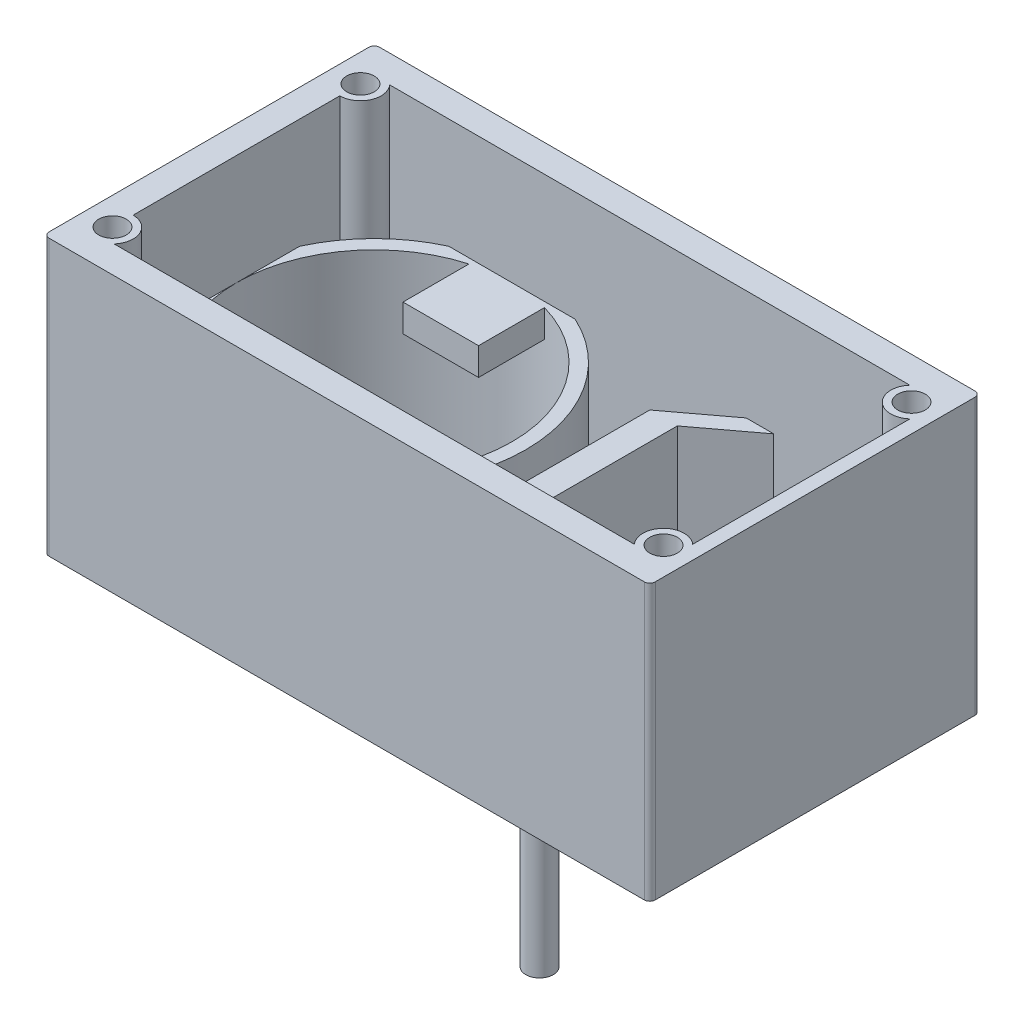
SolidWorks part; units mm, degrees
ref_plane "Front Plane" through (0, 0, 0) normal (0, 0, 1) x (1, 0, 0)
ref_plane "Top Plane" through (0, 0, 0) normal (0, 1, 0) x (1, 0, 0)
ref_plane "Right Plane" through (0, 0, 0) normal (1, 0, 0) x (0, 0, -1)
sketch "Sketch1" plane through (0, 0, 0) normal (0, 1, 0) x (1, 0, 0)
  line L1 (-11, -6) -> (11, -6)
  line L2 (-11, -6) -> (-11, 6)
  line L3 (-11, 6) -> (11, 6)
  line L4 (11, -6) -> (11, 6)
  line L5 (-11, -6) -> (11, 6) construction
  line L6 (-11, 6) -> (11, -6) construction
  point P0 (0, 0)
  dimension "D1" = 12
  dimension "D2" = 22
extrude "Boss-Extrude1" add sketch "Sketch1" along normal blind 10
sketch "Sketch2" plane through (0, 10, 0) normal (0, 1, 0) x (1, 0, 0)
  line L0 (11, 6) -> (-11, 6) construction
  line L1 (10.5, -5) -> (-10, -5)
  line L2 (10.5, -5) -> (10.5, 5)
  line L3 (10.5, 5) -> (-10, 5)
  line L4 (-10, -5) -> (-10, 5)
  line L5 (10.5, -5) -> (-10, 5) construction
  line L6 (10.5, 5) -> (-10, -5) construction
  line L7 (11, -6) -> (11, 6) construction
  point P0 (0.25, 0)
  dimension "D1" = 20.5
  dimension "D2" = 10
  dimension "D3" = 1
  dimension "D4" = 0.5
extrude "Cut-Extrude1" cut sketch "Sketch2" against normal blind 9 contours L4 L3 L2 L1
fillet "Fillet1" radius 0.2 4 edges at (-11, 5, -6) (11, 5, -6) (11, 5, 6) (-11, 5, 6)
sketch "Sketch3" plane through (0, 0, 0) normal (0, -1, 0) x (-1, 0, 0)
  circle A0 centre (5, 0) radius 5
extrude "Cut-Extrude2" cut sketch "Sketch3" against normal through all
sketch "Sketch4" plane through (0, 0, 0) normal (0, -1, 0) x (-1, 0, 0)
  circle A0 centre (-1, 0) radius 0.5
  point P2 (0, 0)
  point P3 (0, 0)
extrude "Cut-Extrude3" cut sketch "Sketch4" against normal through all
sketch "Sketch5" plane through (0, 0, 0) normal (0, -1, 0) x (-1, 0, 0)
  line L0 (-10.5, -5) -> (-10.5, 5) construction
  circle A0 centre (-6.5, 0) radius 2
  point P4 (0, 0)
  dimension "D1" = 4
extrude "Cut-Extrude4" cut sketch "Sketch5" against normal through all
sketch "Sketch6" plane through (0, 1, 0) normal (0, 1, 0) x (1, 0, 0)
  line L0 (2.5, 9.9437) -> (2.5, -10.995) construction
  line L1 (10.5, -5) -> (10.5, 5) construction
  line L2 (-14.9978, 3.5) -> (28.4787, 3.5) construction
  line L3 (20.7123, -3.5) -> (-19.3378, -3.5) construction
  line L4 (0, 0) -> (34.8745, 0) construction
  line L5 (1.5, 9.9437) -> (1.5, -10.995) construction
  line L6 (4.5, 12.7723) -> (4.5, -14.9146) construction
  line L7 (3.5, 10.9096) -> (3.5, -15.2533) construction
  line L8 (2.5, -3.5) -> (2.5, 3.5)
  line L9 (2.5, 3.5) -> (4.5, 5)
  line L10 (10.5, 5) -> (-5, 5) construction
  line L11 (4.5, 5) -> (3.5, 5)
  line L12 (3.5, 5) -> (1.5, 3.5)
  line L13 (1.5, 3.5) -> (1.5, -3.5)
  line L14 (1.5, -3.5) -> (3.5, -5)
  line L15 (10.5, -5) -> (-5, -5) construction
  line L16 (3.5, -5) -> (4.5, -5)
  line L17 (4.5, -5) -> (2.5, -3.5)
  dimension "D1" = 8
  dimension "D2" = 3.5
  dimension "D3" = 3.5
  dimension "D4" = 1
  dimension "D5" = 2
  dimension "D6" = 1
extrude "Boss-Extrude2" add sketch "Sketch6" along normal blind 5
sketch "Sketch9" plane through (0, 1, 0) normal (0, 1, 0) x (1, 0, 0)
  circle A0 centre (-5, 0) radius 5.5
  circle A1 centre (-5, 0) radius 5
extrude "Boss-Extrude3" add sketch "Sketch9" along normal blind 5
sketch "Sketch10" plane through (0, 1, 0) normal (0, 1, 0) x (1, 0, 0)
  circle A0 centre (1, 0) radius 1
  circle A1 centre (1, 0) radius 0.5
extrude "Boss-Extrude4" add sketch "Sketch10" along normal blind 2
sketch "Sketch12" plane through (0, 3, 0) normal (0, 1, 0) x (1, 0, 0)
  circle A0 centre (1, 0) radius 0.5
extrude "Boss-Extrude6" add sketch "Sketch12" against normal blind 1
sketch "Sketch13" plane through (0, 1, 0) normal (0, 1, 0) x (1, 0, 0)
  circle A0 centre (10, 4.5) radius 0.75
  circle A1 centre (10, 4.5) radius 0.5
extrude "Boss-Extrude7" add sketch "Sketch13" along normal blind 9
sketch "Sketch14" plane through (0, 0, 0) normal (0, -1, 0) x (-1, 0, 0)
  circle A0 centre (-10, 4.5) radius 0.5
  point P2 (0, 0)
extrude "Cut-Extrude5" cut sketch "Sketch14" against normal through all
mirror "Mirror1" about plane through (0, 0, 0) normal (1, 0, 0) of "Cut-Extrude5", "Boss-Extrude7"
mirror "Mirror2" about plane through (0, 0, 0) normal (0, 0, 1) of "Mirror1"
sketch "Sketch15" plane through (0, 6, 0) normal (0, 1, 0) x (1, 0, 0)
  line L0 (-6.3706, 2.4148) -> (-6.3706, 5.5363)
  line L1 (-6.3706, -5.5363) -> (-3.6294, -5.5363)
  line L2 (-6.3706, -5.5363) -> (-6.3706, -2.4148)
  line L3 (-6.3706, 5.5363) -> (-3.6294, 5.5363)
  line L4 (-3.6294, -5.5363) -> (-3.6294, -2.4148)
  line L7 (-6.3706, -2.4148) -> (-3.6294, -2.4148)
  line L9 (-6.3706, 2.4148) -> (-3.6294, 2.4148)
  line L15 (-3.6294, 2.4148) -> (-3.6294, 5.5363)
  point P0 (-5, 0)
  point P1 (-5, 0)
  point P9 (-5, 0)
extrude "Boss-Extrude8" add sketch "Sketch15" against normal blind 1
sketch "Sketch16" plane through (0, 0, 0) normal (0, -1, 0) x (1, 0, 0)
  circle A0 centre (1, 0) radius 0.5
extrude "Boss-Extrude9" add sketch "Sketch16" along normal blind 10 separate body
